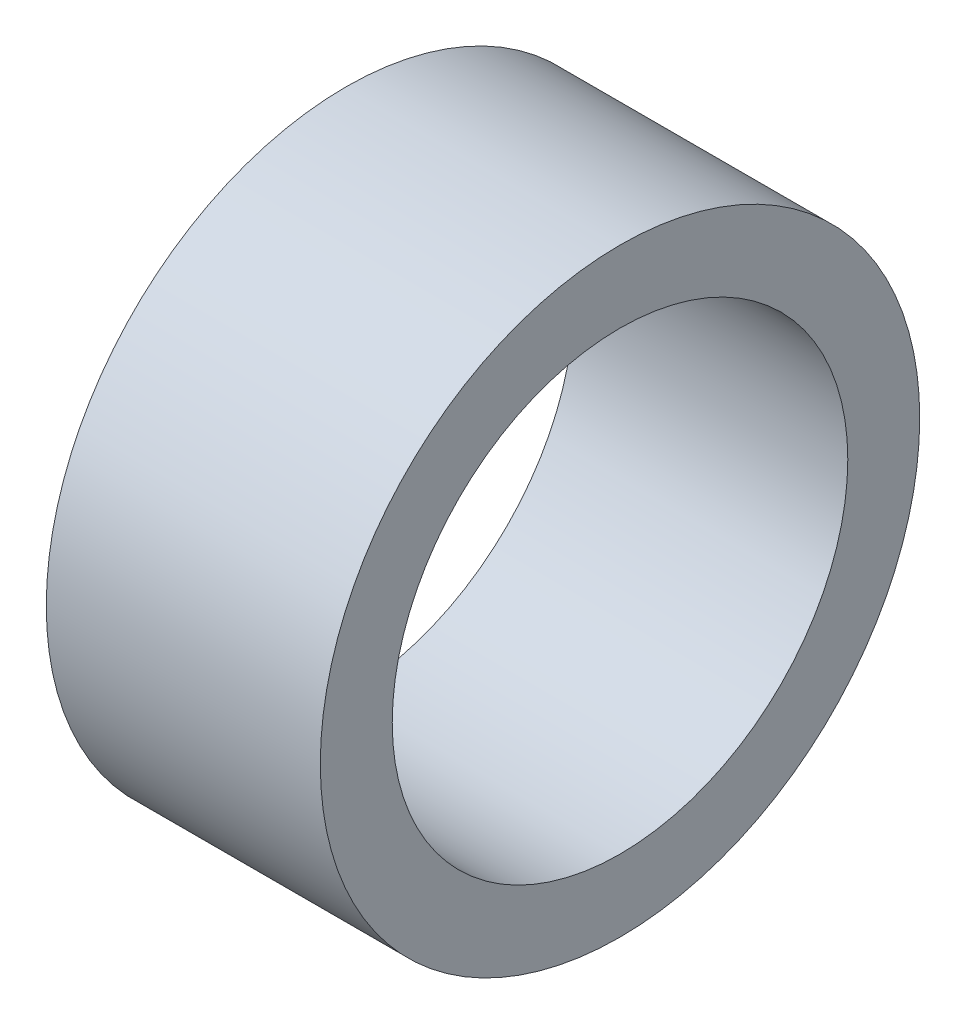
SolidWorks part; units mm, degrees
material "Nylon 6/10"
ref_plane "Front Plane" through (0, 0, 0) normal (0, 0, 1) x (1, 0, 0)
ref_plane "Top Plane" through (0, 0, 0) normal (0, 1, 0) x (1, 0, 0)
ref_plane "Right Plane" through (0, 0, 0) normal (1, 0, 0) x (0, 0, -1)
sketch "Sketch1" plane through (0, 0, 0) normal (0, 0, 1) x (1, 0, 0)
  line L0 (38.1, -11.935) -> (38.1, 10.1355) construction
  line L1 (38.1, 5.5563) -> (43.18, 5.5563)
  line L2 (38.1, 5.5563) -> (38.1, 4.2228)
  line L3 (38.1, 4.2228) -> (43.18, 4.2228)
  line L4 (43.18, 5.5563) -> (43.18, 4.2228)
  line L5 (0, 0) -> (42.6651, 0) construction
  line L7 (44.1854, 3.9688) -> (-54.7878, 3.9688) construction
  dimension "D1" = 0.254
  dimension "D2" = 11.1125
  dimension "D3" = 5.08
revolve "Revolve1" add sketch "Sketch1" angle 360 about L5
